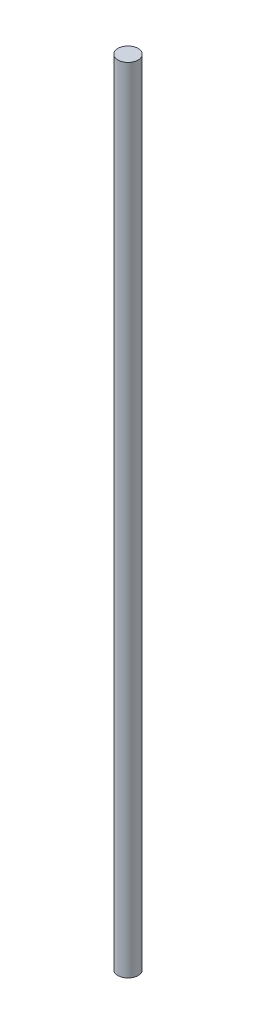
SolidWorks part; units mm, degrees
material "Plain Carbon Steel"
ref_plane "Front Plane" through (0, 0, 0) normal (0, 0, 1) x (1, 0, 0)
ref_plane "Top Plane" through (0, 0, 0) normal (0, 1, 0) x (1, 0, 0)
ref_plane "Right Plane" through (0, 0, 0) normal (1, 0, 0) x (0, 0, -1)
sketch "Sketch1" plane through (0, 0, 0) normal (0, 1, 0) x (1, 0, 0)
  circle A0 centre (0, 0) radius 4.7625
  dimension "D1" = 9.525
extrude "Boss-Extrude1" add sketch "Sketch1" along normal blind 374.65
equation "\"Mid_Coupler_Length\" = 13in"
equation "\"Lead_Screw_Length\" = (\"Mid_Coupler_Length\" + 2*0.375in + 2*0.5in)"
equation "\"D1@Boss-Extrude1\"=\"Lead_Screw_Length\""
